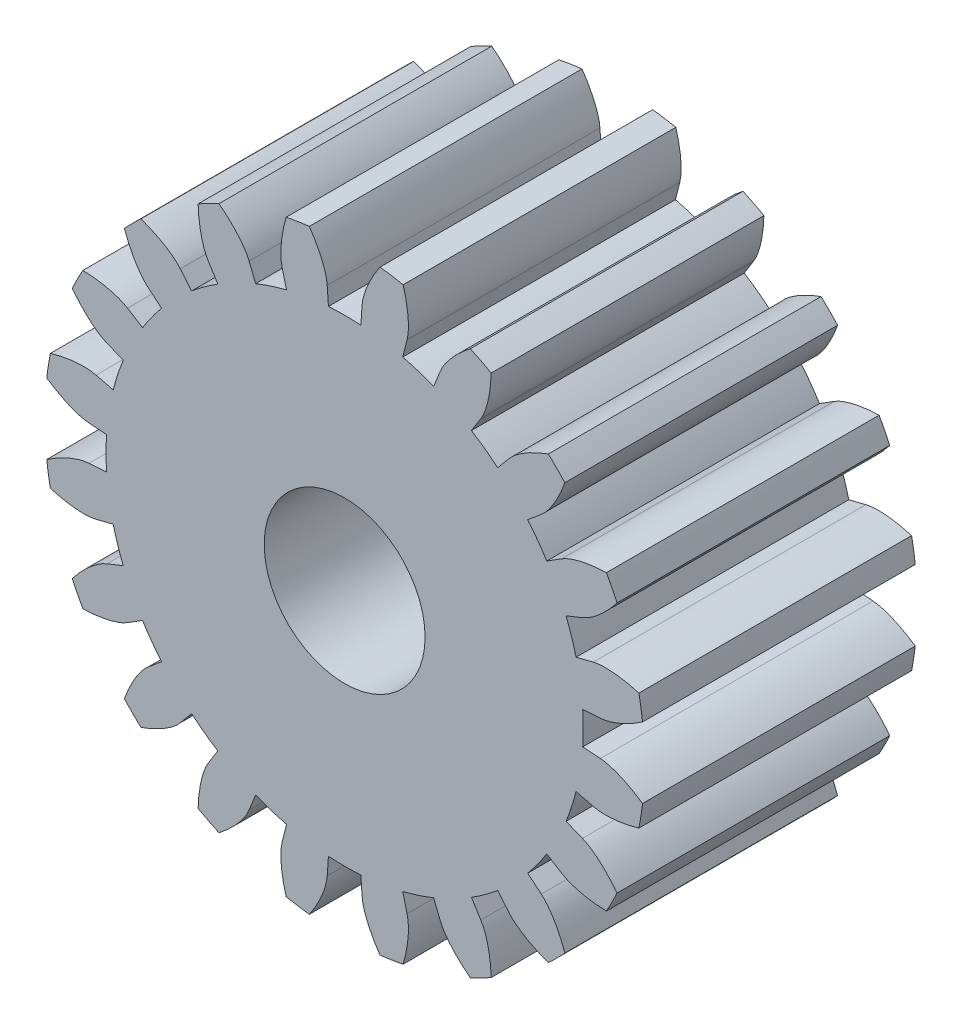
SolidWorks part; units mm, degrees
ref_plane "前视基准面" through (0, 0, 0) normal (0, 0, 1) x (1, 0, 0)
ref_plane "上视基准面" through (0, 0, 0) normal (0, 1, 0) x (1, 0, 0)
ref_plane "右视基准面" through (0, 0, 0) normal (1, 0, 0) x (0, 0, -1)
other "Configuration Table"
sketch "草图1" plane through (0, 0, 0) normal (0, 0, 1) x (1, 0, 0)
  line L0 (0, 0) -> (5, 0) construction
  line L1 (0, 0) -> (4.9846, 0.3923) construction
  line L2 (0, 0) -> (4.6876, 0.3194)
  line L3 (4.9846, 0.3923) -> (4.9846, -0.3923) construction
  line L4 (0, 0) -> (4.6876, -0.3194)
  circle A0 centre (0, 0) radius 5.5
  circle A1 centre (0, 0) radius 5 construction
  circle A2 centre (0, 0) radius 4.375
  circle A3 centre (0, 0) radius 4.6985 construction
  circle A4 centre (0, 0) radius 1.475
  spline S0 degree 4 poles (4.6876, 0.3194) (4.7233, 0.3218) (4.8225, 0.336) (5.0062, 0.3926) (5.2885, 0.5242) (5.6241, 0.7499) (6.0094, 1.0976) (6.395, 1.5688) (6.7398, 2.1414) (7.0933, 2.9696) (7.3065, 3.8467) (7.3947, 4.7795) (7.347, 5.8934) (7.1568, 6.9938) (6.7515, 8.227) (6.0949, 9.5107) (5.2611, 10.6861) (4.2765, 11.7378) (3.1662, 12.6551) (1.9531, 13.4307) (0.6586, 14.0604) (-0.5283, 14.4821) (-1.4854, 14.7287) (-2.1912, 14.8654) (-2.6338, 14.9356) (-2.9917, 14.9827) (-3.3451, 15.0208) (-3.7095, 15.05) (-4.0266, 15.0684) (-4.3306, 15.0786) (-4.6986, 15.0842) (-4.9527, 15.0816) (-5.4001, 15.0704) (-5.6957, 15.0494) (-6.0237, 15.027) (-6.2862, 14.9991) (-6.5922, 14.9657) (-6.7961, 14.9366) (-6.9439, 14.9154) (-7.0152, 14.9043) knots 0 0 0 0 0 0.005604 0.015718 0.02996 0.048734 0.068727 0.096889 0.125051 0.153212 0.209535 0.237696 0.271429 0.327752 0.384075 0.440398 0.496721 0.553044 0.609367 0.66569 0.722013 0.778336 0.806497 0.820578 0.834659 0.84874 0.86282 0.876901 0.890982 0.900036 0.909091 0.931818 0.943182 0.954545 0.965909 0.977273 0.988636 1 1 1 1 1 construction
  spline S1 degree 4 poles (4.6876, 0.3194) (4.7233, 0.3218) (4.8225, 0.336) (5.0062, 0.3926) (5.2885, 0.5242) (5.6241, 0.7499) (6.0094, 1.0976) (6.395, 1.5688) (6.7398, 2.1414) (7.0933, 2.9696) (7.3065, 3.8467) (7.3947, 4.7795) (7.347, 5.8934) (7.1568, 6.9938) (6.7515, 8.227) (6.0949, 9.5107) (5.2611, 10.6861) (4.2765, 11.7378) (3.1662, 12.6551) (1.9531, 13.4307) (0.6586, 14.0604) (-0.5283, 14.4821) (-1.4854, 14.7287) (-2.1912, 14.8654) (-2.6338, 14.9356) (-2.9917, 14.9827) (-3.3451, 15.0208) (-3.7095, 15.05) (-4.0266, 15.0684) (-4.3306, 15.0786) (-4.5463, 15.0819) (-4.6529, 15.0825) (-4.7054, 15.0825) knots 0 0 0 0 0 0.005604 0.015718 0.02996 0.048734 0.068727 0.096889 0.125051 0.153212 0.209535 0.237696 0.271429 0.327752 0.384075 0.440398 0.496721 0.553044 0.609367 0.66569 0.722013 0.778336 0.806497 0.820578 0.834659 0.84874 0.86282 0.876901 0.890982 0.900036 0.909091 0.909091 0.909091 0.909091 0.909091
  spline S2 degree 4 poles (4.6876, -0.3194) (4.7233, -0.3218) (4.8225, -0.336) (5.0062, -0.3926) (5.2885, -0.5242) (5.6241, -0.7499) (6.0094, -1.0976) (6.395, -1.5688) (6.7398, -2.1414) (7.0933, -2.9696) (7.3065, -3.8467) (7.3947, -4.7795) (7.347, -5.8934) (7.1568, -6.9938) (6.7515, -8.227) (6.0949, -9.5107) (5.2611, -10.6861) (4.2765, -11.7378) (3.1662, -12.6551) (1.9531, -13.4307) (0.6586, -14.0604) (-0.5283, -14.4821) (-1.4854, -14.7287) (-2.1912, -14.8654) (-2.6338, -14.9356) (-2.9917, -14.9827) (-3.3451, -15.0208) (-3.7095, -15.05) (-4.0266, -15.0684) (-4.3306, -15.0786) (-4.6986, -15.0842) (-4.9527, -15.0816) (-5.4001, -15.0704) (-5.6957, -15.0494) (-6.0237, -15.027) (-6.2862, -14.9991) (-6.5922, -14.9657) (-6.7961, -14.9366) (-6.9439, -14.9154) (-7.0152, -14.9043) knots 0 0 0 0 0 0.005604 0.015718 0.02996 0.048734 0.068727 0.096889 0.125051 0.153212 0.209535 0.237696 0.271429 0.327752 0.384075 0.440398 0.496721 0.553044 0.609367 0.66569 0.722013 0.778336 0.806497 0.820578 0.834659 0.84874 0.86282 0.876901 0.890982 0.900036 0.909091 0.931818 0.943182 0.954545 0.965909 0.977273 0.988636 1 1 1 1 1 construction
  spline S3 degree 4 poles (4.6876, -0.3194) (4.7233, -0.3218) (4.8225, -0.336) (5.0062, -0.3926) (5.2885, -0.5242) (5.6241, -0.7499) (6.0094, -1.0976) (6.395, -1.5688) (6.7398, -2.1414) (7.0933, -2.9696) (7.3065, -3.8467) (7.3947, -4.7795) (7.347, -5.8934) (7.1568, -6.9938) (6.7515, -8.227) (6.0949, -9.5107) (5.2611, -10.6861) (4.2765, -11.7378) (3.1662, -12.6551) (1.9531, -13.4307) (0.6586, -14.0604) (-0.5283, -14.4821) (-1.4854, -14.7287) (-2.1912, -14.8654) (-2.6338, -14.9356) (-2.9917, -14.9827) (-3.3451, -15.0208) (-3.7095, -15.05) (-4.0266, -15.0684) (-4.3306, -15.0786) (-4.5463, -15.0819) (-4.6529, -15.0825) (-4.7054, -15.0825) knots 0 0 0 0 0 0.005604 0.015718 0.02996 0.048734 0.068727 0.096889 0.125051 0.153212 0.209535 0.237696 0.271429 0.327752 0.384075 0.440398 0.496721 0.553044 0.609367 0.66569 0.722013 0.778336 0.806497 0.820578 0.834659 0.84874 0.86282 0.876901 0.890982 0.900036 0.909091 0.909091 0.909091 0.909091 0.909091
  point P15 (4.9846, 0)
  dimension "齿顶圆直径" = 11
  dimension "分度圆直径" = 10
  dimension "齿根圆直径" = 8.75
  dimension "基圆直径" = 9.3969
  dimension "内孔直径" = 2.95
  dimension "渐近线镜像线夹角" = 4.5
extrude "凸台-拉伸1" add sketch "草图1" along normal blind 5 contours A0 | A4
extrude "切除-拉伸1" cut sketch "草图1<3>" along normal through all contours A2 S3 A0 S1 region at (5.0102, 0, 0)
sketch "草图1<3>" plane through (0, 0, 0) normal (0, 0, 1) x (1, 0, 0) same geometry as "草图1"
pattern_circular "阵列(圆周)1" count 20 every 18 about axis through (0, 0, 5) along (0, 0, 1) of "切除-拉伸1"
equation "\"m\"= 0.5'模数"
equation "\"z\"= 20'齿数"
equation "\"a\"= 20度'压力角"
equation "\"d\"= \"m\" * \"z\"'分度圆直径"
equation "\"da\"= ( \"z\" + 2 ) * \"m\"'齿顶圆直径"
equation "\"df\"= ( \"z\" - 2.5 ) * \"m\"'齿根圆直径"
equation "\"s\"= 0.5 * PI * \"m\"'分度圆齿厚"
equation "\"r\"= 0.38 * \"m\"'齿根圆角"
equation "\"B\"= 0.3 * \"d\"'齿厚"
equation "\"db\"= \"m\" * \"z\" * cos ( \"a\" )'基圆直径"
equation "\"rb\"= \"db\" / 2'基圆半径"
equation "\"齿顶圆直径@草图1\"= \"da\""
equation "\"分度圆直径@草图1\"= \"d\""
equation "\"齿根圆直径@草图1\"= \"df\""
equation "\"基圆直径@草图1\"= \"db\""
equation "\"渐近线镜像线夹角@草图1\"= 360 / 4 / \"z\""
equation "\"h\"= 5'齿轮厚度"
equation "\"ir\"= 2.95'内孔直径"
equation "\"内孔直径@草图1\"= \"ir\""
equation "\"齿轮厚@凸台-拉伸1\"= \"h\""
equation "\"齿轮夹角@阵列(圆周)1\"= 360 / \"z\""
equation "\"齿数@阵列(圆周)1\"= \"z\""
